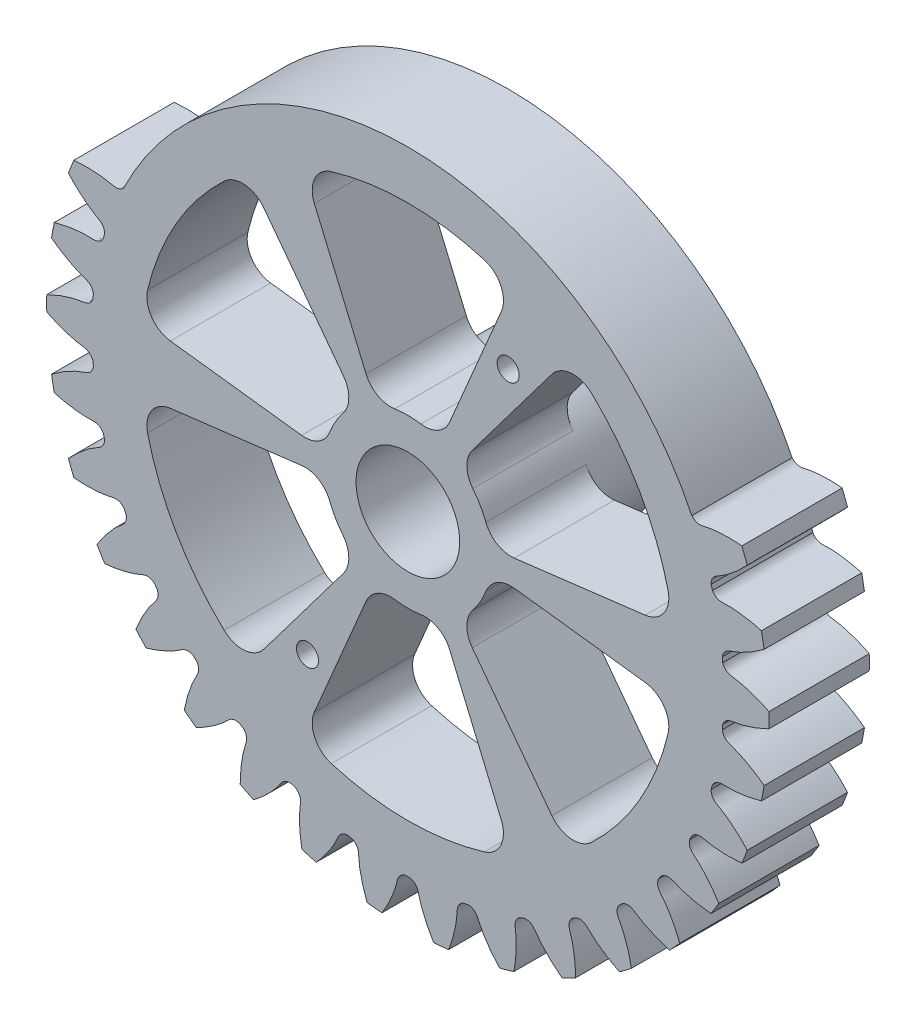
SolidWorks part; units mm, degrees
material "POM 乙缩醛共聚物"
ref_plane "前视基准面" through (0, 0, 0) normal (0, 0, 1) x (1, 0, 0)
ref_plane "上视基准面" through (0, 0, 0) normal (0, 1, 0) x (1, 0, 0)
ref_plane "右视基准面" through (0, 0, 0) normal (1, 0, 0) x (0, 0, -1)
sketch "草图1" plane through (0, 0, 0) normal (0, 0, 1) x (1, 0, 0)
  circle A0 centre (0, 0) radius 54
extrude "凸台-拉伸1" add sketch "草图1" along normal blind 15
ref_axis "基准轴1" through (0, 0, -0.75) along (0, 0, 1)
sketch "草图2" plane through (0, 0, 0) normal (0, 0, 1) x (1, 0, 0)
  line L0 (0, 0) -> (0, 54) construction
  circle A0 centre (0, 0) radius 54 construction
  arc A1 (0.3663, 47.2486) -> (-0.3663, 47.2486) centre (0, 0) ccw
  arc A2 (10.1147, 61.1098) -> (-10.1147, 61.1098) centre (0, 0) ccw
  spline S0 degree 3 poles (0.3663, 47.2486) (1.4332, 47.5502) (1.5268, 48.3776) (1.7599, 49.2473) (1.8259, 49.4765) (1.9022, 49.7226) (1.9894, 49.9854) (2.0882, 50.2644) (2.1994, 50.5594) (2.3236, 50.8699) (2.4614, 51.1954) (2.6135, 51.5357) (2.7806, 51.8902) (2.9632, 52.2585) (3.162, 52.64) (3.3776, 53.0343) (3.6106, 53.4409) (3.8615, 53.8591) (4.1309, 54.2885) (4.4194, 54.7285) (4.7274, 55.1784) (5.0555, 55.6377) (5.4042, 56.1057) (5.7739, 56.5817) (6.1651, 57.0652) (6.5783, 57.5554) (7.0138, 58.0517) (7.4721, 58.5533) (7.9536, 59.0596) (8.4585, 59.5697) (9.1728, 60.263) (9.7312, 60.773) (10.1147, 61.1098) knots 0 0 0 0 0.130724 0.143504 0.157401 0.172415 0.188546 0.205794 0.224159 0.243641 0.26424 0.285956 0.308788 0.332738 0.357805 0.383988 0.411289 0.439706 0.46924 0.499892 0.53166 0.564545 0.598547 0.633666 0.669902 0.707255 0.745725 0.785312 0.826016 0.867836 0.910774 1 1 1 1
  spline S1 degree 3 poles (-0.3663, 47.2486) (-1.4332, 47.5502) (-1.5268, 48.3776) (-1.7599, 49.2473) (-1.8259, 49.4765) (-1.9022, 49.7226) (-1.9894, 49.9854) (-2.0882, 50.2644) (-2.1994, 50.5594) (-2.3236, 50.8699) (-2.4614, 51.1954) (-2.6135, 51.5357) (-2.7806, 51.8902) (-2.9632, 52.2585) (-3.162, 52.64) (-3.3776, 53.0343) (-3.6106, 53.4409) (-3.8615, 53.8591) (-4.1309, 54.2885) (-4.4194, 54.7285) (-4.7274, 55.1784) (-5.0555, 55.6377) (-5.4042, 56.1057) (-5.7739, 56.5817) (-6.1651, 57.0652) (-6.5783, 57.5554) (-7.0138, 58.0517) (-7.4721, 58.5533) (-7.9536, 59.0596) (-8.4585, 59.5697) (-9.1728, 60.263) (-9.7312, 60.773) (-10.1147, 61.1098) knots 0 0 0 0 0.130724 0.143504 0.157401 0.172415 0.188546 0.205794 0.224159 0.243641 0.26424 0.285956 0.308788 0.332738 0.357805 0.383988 0.411289 0.439706 0.46924 0.499892 0.53166 0.564545 0.598547 0.633666 0.669902 0.707255 0.745725 0.785312 0.826016 0.867836 0.910774 1 1 1 1
extrude "切除-拉伸1" cut sketch "草图2" along normal through all
pattern_circular "阵列(圆周)1" count 34 every 10.588 about axis through (0, 0, -0.75) along (0, 0, 1) of "切除-拉伸1"
sketch "草图3" plane through (0, 0, 0) normal (0, 0, 1) x (1, 0, 0)
  circle A0 centre (0, 0) radius 51 construction
  dimension "Dn" = 102
sketch "草图4" plane through (0, 0, 0) normal (0, 0, -1) x (-1, 0, 0)
  line L0 (-13.9792, 32.933) -> (-6.2547, 14.7353)
  line L1 (6.2547, 14.7353) -> (13.9792, 32.933)
  line L2 (0, 0) -> (0, 45.32) construction
  line L3 (21.5312, 28.5729) -> (9.6337, 12.7844)
  line L4 (15.8885, 1.9509) -> (35.5104, 4.3601)
  line L5 (0, 0) -> (39.2482, 22.66) construction
  line L6 (35.5104, -4.3601) -> (15.8885, -1.9509)
  line L7 (9.6337, -12.7844) -> (21.5312, -28.5729)
  line L8 (0, 0) -> (39.2482, -22.66) construction
  line L9 (13.9792, -32.933) -> (6.2547, -14.7353)
  line L10 (-6.2547, -14.7353) -> (-13.9792, -32.933)
  line L11 (0, 0) -> (0, -45.32) construction
  line L12 (-21.5312, -28.5729) -> (-9.6337, -12.7844)
  line L13 (-15.8885, -1.9509) -> (-35.5104, -4.3601)
  line L14 (0, 0) -> (-39.2482, -22.66) construction
  line L15 (-35.5104, 4.3601) -> (-15.8885, 1.9509)
  line L16 (-9.6337, 12.7844) -> (-21.5312, 28.5729)
  line L17 (0, 0) -> (-39.2482, 22.66) construction
  circle A0 centre (0, 0) radius 7.75
  arc A1 (-1.949, 12.3471) -> (1.949, 12.3471) centre (0, 0) cw
  arc A2 (-11.4413, 38.3288) -> (11.4413, 38.3288) centre (0, 0) cw
  arc A3 (-1.949, 12.3471) -> (-6.2547, 14.7353) centre (-2.5727, 16.2982) cw
  arc A4 (1.949, 12.3471) -> (6.2547, 14.7353) centre (2.5727, 16.2982) ccw
  arc A5 (11.4413, 38.3288) -> (13.9792, 32.933) centre (10.2972, 34.4959) cw
  arc A6 (-11.4413, 38.3288) -> (-13.9792, 32.933) centre (-10.2972, 34.4959) ccw
  arc A7 (9.7184, 7.8615) -> (11.6674, 4.4856) centre (0, 0) cw
  arc A8 (27.473, 29.0729) -> (38.9144, 9.2559) centre (0, 0) cw
  arc A9 (9.7184, 7.8615) -> (9.6337, 12.7844) centre (12.8283, 10.3771) cw
  arc A10 (11.6674, 4.4856) -> (15.8885, 1.9509) centre (15.401, 5.921) ccw
  arc A11 (38.9144, 9.2559) -> (35.5104, 4.3601) centre (35.0229, 8.3303) cw
  arc A12 (27.473, 29.0729) -> (21.5312, 28.5729) centre (24.7257, 26.1656) ccw
  arc A13 (11.6674, -4.4856) -> (9.7184, -7.8615) centre (0, 0) cw
  arc A14 (38.9144, -9.2559) -> (27.473, -29.0729) centre (0, 0) cw
  arc A15 (11.6674, -4.4856) -> (15.8885, -1.9509) centre (15.401, -5.921) cw
  arc A16 (9.7184, -7.8615) -> (9.6337, -12.7844) centre (12.8283, -10.3771) ccw
  arc A17 (27.473, -29.0729) -> (21.5312, -28.5729) centre (24.7257, -26.1656) cw
  arc A18 (38.9144, -9.2559) -> (35.5104, -4.3601) centre (35.0229, -8.3303) ccw
  arc A19 (1.949, -12.3471) -> (-1.949, -12.3471) centre (0, 0) cw
  arc A20 (11.4413, -38.3288) -> (-11.4413, -38.3288) centre (0, 0) cw
  arc A21 (1.949, -12.3471) -> (6.2547, -14.7353) centre (2.5727, -16.2982) cw
  arc A22 (-1.949, -12.3471) -> (-6.2547, -14.7353) centre (-2.5727, -16.2982) ccw
  arc A23 (-11.4413, -38.3288) -> (-13.9792, -32.933) centre (-10.2972, -34.4959) cw
  arc A24 (11.4413, -38.3288) -> (13.9792, -32.933) centre (10.2972, -34.4959) ccw
  arc A25 (-9.7184, -7.8615) -> (-11.6674, -4.4856) centre (0, 0) cw
  arc A26 (-27.473, -29.0729) -> (-38.9144, -9.2559) centre (0, 0) cw
  arc A27 (-9.7184, -7.8615) -> (-9.6337, -12.7844) centre (-12.8283, -10.3771) cw
  arc A28 (-11.6674, -4.4856) -> (-15.8885, -1.9509) centre (-15.401, -5.921) ccw
  arc A29 (-38.9144, -9.2559) -> (-35.5104, -4.3601) centre (-35.0229, -8.3303) cw
  arc A30 (-27.473, -29.0729) -> (-21.5312, -28.5729) centre (-24.7257, -26.1656) ccw
  arc A31 (-11.6674, 4.4856) -> (-9.7184, 7.8615) centre (0, 0) cw
  arc A32 (-38.9144, 9.2559) -> (-27.473, 29.0729) centre (0, 0) cw
  arc A33 (-11.6674, 4.4856) -> (-15.8885, 1.9509) centre (-15.401, 5.921) cw
  arc A34 (-9.7184, 7.8615) -> (-9.6337, 12.7844) centre (-12.8283, 10.3771) ccw
  arc A35 (-27.473, 29.0729) -> (-21.5312, 28.5729) centre (-24.7257, 26.1656) cw
  arc A36 (-38.9144, 9.2559) -> (-35.5104, 4.3601) centre (-35.0229, 8.3303) ccw
  point P83 (0, 0)
  dimension "D1" = 15.5
  dimension "D2" = 12.5
  dimension "D3" = 40
  dimension "D5" = 4
  dimension "D4" = 46
  dimension "D6" = 6
extrude "切除-拉伸2" cut sketch "草图4" against normal through all
sketch "草图5" plane through (0, 0, 0) normal (0, 0, -1) x (-1, 0, 0)
  line L0 (0, 0) -> (-22.7126, 39.3394) construction
  line L1 (-13.9792, 32.933) -> (-6.2547, 14.7353) construction
  line L2 (0, 0) -> (25.7646, 14.8752) construction
  circle A0 centre (-15, 25.9808) radius 1.65
  circle A2 centre (15, -25.9808) radius 1.65
  dimension "D2" = 3.3
  dimension "D3" = 30
  dimension "D1" = 7
extrude "切除-拉伸3" cut sketch "草图5" against normal through all
sketch "草图6" plane through (0, 0, 0) normal (0, 0, -1) x (-1, 0, 0)
  circle A0 centre (0, 0) radius 12.5
  circle A1 centre (0, 0) radius 7.75
extrude "凸台-拉伸2" add sketch "草图6" along normal blind 10
sketch "草图7" plane through (0, 0, 0) normal (0, 1, 0) x (1, 0, 0)
  line L0 (0, 10) -> (0, 0) construction
  line L1 (12.5, 10) -> (-12.5, 10) construction
  circle A0 centre (0, 5) radius 1.65
  dimension "D1" = 3.3
  dimension "D2" = 5
extrude "切除-拉伸4" cut sketch "草图7" against normal mid plane 50
sketch "草图8" plane through (0, 0, 15) normal (0, 0, 1) x (1, 0, 0)
  line L2 (-48.1135, 24.5172) -> (-42.1319, 21.3884)
  line L3 (48.132, 24.4809) -> (42.4585, 20.7326)
  arc A0 (-42.1319, 21.3884) -> (42.4585, 20.7326) centre (0, 0) cw
  arc A1 (-48.1135, 24.5172) -> (48.132, 24.4809) centre (0, 0) cw
  arc A3 (-23.061, 48.8282) -> (-25.0684, 47.8286) centre (0, 0) ccw construction
  point P5 (0, 0)
  point P6 (-42.4585, 20.7326)
  point P10 (-48.2508, 24.2459)
  point P11 (0, 0)
  point P12 (45.5451, 12.5778)
  point P13 (52.303, 13.431)
  point P14 (0, 0)
  point P15 (-47.0808, -3.9948)
  point P16 (-53.852, -3.9948)
  point P17 (0, 0)
  point P18 (37.4844, 28.766)
  point P19 (43.8803, 31.4726)
  point P22 (0, 0)
  point P24 (-47.0808, -3.9957)
  point P27 (-45.3446, 13.2825)
  point P28 (-52.1052, 14.179)
  point P34 (0, 0)
  point P35 (-42.1319, 21.3884)
  point P37 (-48.1135, 24.5172)
  point P38 (0, 0)
  point P39 (45.5451, 12.5778)
  point P41 (51.6531, 15.7467)
  point P42 (0, 0)
  point P43 (42.4585, 20.7326)
  point P45 (48.132, 24.5172)
extrude "切除-拉伸5" cut sketch "草图8" against normal through all
